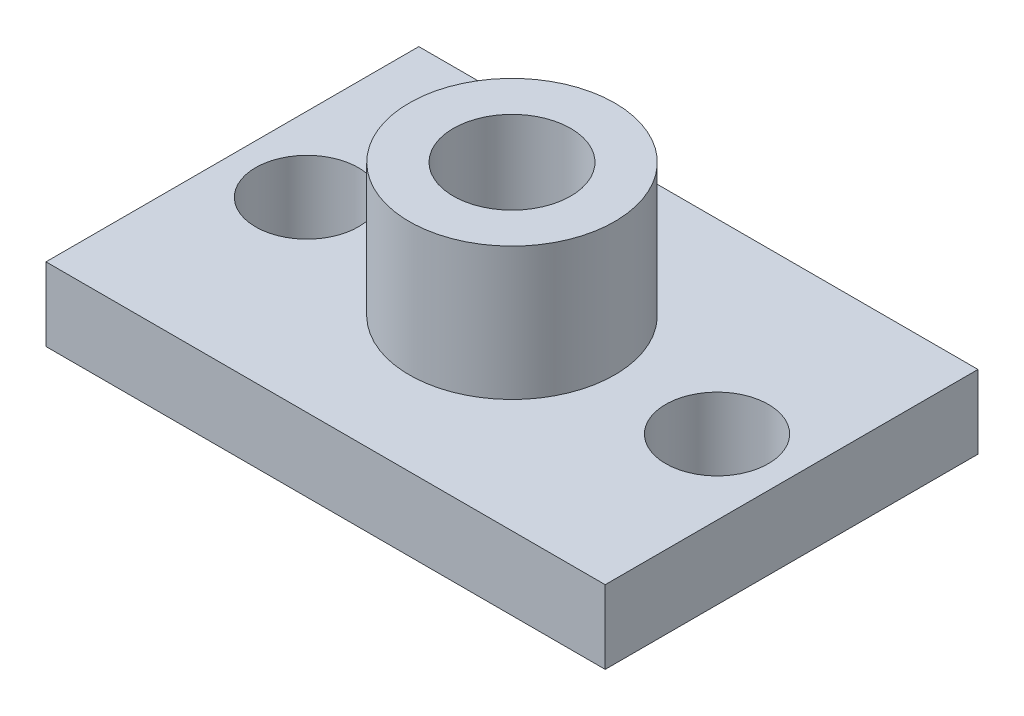
SolidWorks part; units mm, degrees
ref_plane "前视" through (0, 0, 0) normal (0, 0, 1) x (1, 0, 0)
ref_plane "上视" through (0, 0, 0) normal (0, 1, 0) x (1, 0, 0)
ref_plane "右视" through (0, 0, 0) normal (1, 0, 0) x (0, 0, -1)
sketch "Sketch1" plane through (0, 0, 0) normal (0, 1, 0) x (1, 0, 0)
  line L1 (-25.8417, 12.7) -> (12.2583, 12.7)
  line L2 (-25.8417, 12.7) -> (-25.8417, -12.7)
  line L3 (-25.8417, -12.7) -> (12.2583, -12.7)
  line L4 (12.2583, 12.7) -> (12.2583, -12.7)
  dimension "D1" = 25.4
  dimension "D2" = 38.1
extrude "Boss-Extrude1" add sketch "Sketch1" along normal blind 5
ref_point "Point1"
sketch "Sketch3" plane through (0, 5, 0) normal (0, 1, 0) x (1, 0, 0)
  circle A0 centre (-6.7917, 0) radius 7
  circle A1 centre (-6.7917, 0) radius 4
extrude "Boss-Extrude2" add sketch "Sketch3" along normal blind 9.05
ref_axis "Axis1" through (12.2583, 5, 0) along (-1, 0, 0)
sketch "Sketch4" plane through (0, 5, 0) normal (0, 1, 0) x (1, 0, 0)
  line L0 (12.2583, -12.7) -> (12.2583, 12.7) construction
  line L1 (-25.8417, 12.7) -> (-25.8417, -12.7) construction
  circle A0 centre (7.1783, 0) radius 3.5
  circle A1 centre (-20.7617, 0) radius 3.5
  point P0 (7.1783, 0)
  point P1 (12.2583, 0)
  point P4 (-20.7617, 0)
  dimension "D3" = 7
  dimension "D4" = 7
  dimension "D1" = 5.08
  dimension "D2" = 5.08
extrude "Cut-Extrude1" cut sketch "Sketch4" against normal through all
